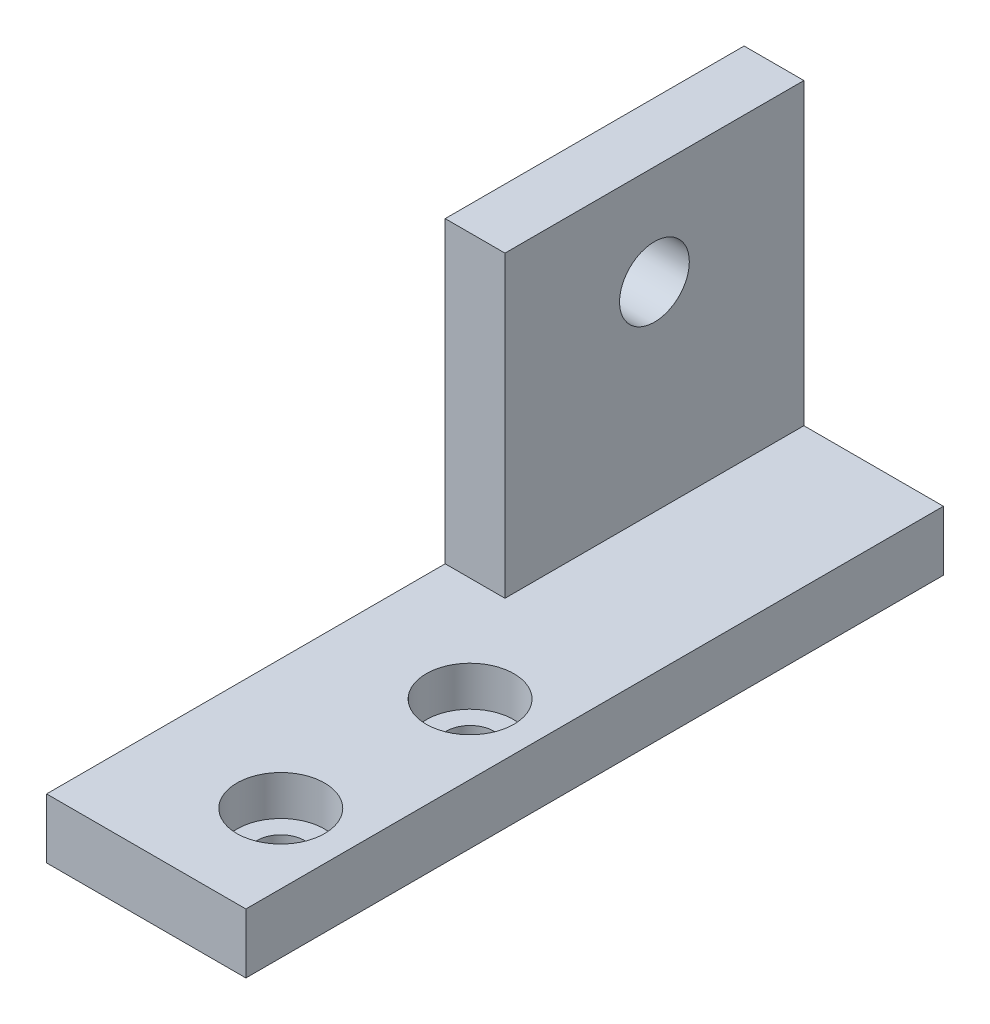
SolidWorks part; units mm, degrees
ref_plane "Front Plane" through (0, 0, 0) normal (0, 0, 1) x (1, 0, 0)
ref_plane "Top Plane" through (0, 0, 0) normal (0, 1, 0) x (1, 0, 0)
ref_plane "Right Plane" through (0, 0, 0) normal (1, 0, 0) x (0, 0, -1)
sketch "Sketch1" plane through (0, 0, 0) normal (0, 1, 0) x (1, 0, 0)
  line L0 (6.5, 5.25) -> (6.5, 14.75) construction
  line L1 (0, 0) -> (10, 0)
  line L2 (0, 0) -> (0, 20)
  line L3 (0, 20) -> (10, 20)
  line L4 (10, 0) -> (10, 20)
  circle A0 centre (6.5, 5.25) radius 1.175
  circle A1 centre (6.5, 14.75) radius 1.175
  point P9 (6.5, 10)
  point P10 (10, 10)
  dimension "D3" = 9.5
  dimension "D4" = 2.35
  dimension "D5" = 2.35
  dimension "D6" = 6.5
  dimension "D1" = 20
  dimension "D2" = 10
extrude "Boss-Extrude1" add sketch "Sketch1" along normal blind 3
sketch "Sketch2" plane through (0, 3, 0) normal (0, 1, 0) x (1, 0, 0)
  point P0 (6.5, 14.75)
  point P1 (6.5, 5.25)
hole_wizard "CBORE for M2 SHCS1" positions "Sketch2" profile "Sketch3" counterbore size "M2" standard "ANSI Metric" end condition through all
sketch "Sketch3" plane through (6.5, 3, -14.75) normal (1, 0, 0) x (0, 0, 1)
  line L0 (0, 0) -> (0, 3)
  line L1 (0, 3) -> (1.2, 3)
  line L3 (1.2, 3) -> (1.2, 2)
  line L4 (1.2, 2) -> (2.2, 2)
  line L5 (2.2, 2) -> (2.2, 0)
  line L7 (2.2, 0) -> (0, 0)
  line L11 (0, -6.35) -> (0, 107.95) construction
  dimension "Thru Hole Dia." = 2.4
  dimension "Thru Hole Depth" = 3
  dimension "C'Bore Dia." = 4.4
  dimension "C'Bore Depth" = 2
sketch "Sketch6" plane through (0, 0, -20) normal (0, 0, -1) x (-1, 0, 0)
  line L1 (0, 0) -> (-10, 0)
  line L2 (0, 0) -> (0, 3)
  line L3 (0, 3) -> (-10, 3)
  line L4 (-10, 0) -> (-10, 3)
  line L5 (-10, 3) -> (0, 3) construction
  line L6 (-10, 3) -> (-10, 0) construction
  point P5 (-10.0485, 3.0247)
  point P6 (-9.5691, 3)
  dimension "D1" = 0
extrude "Boss-Extrude2" add sketch "Sketch6" along normal blind 15
sketch "Sketch8" plane through (0, 3, 0) normal (0, 1, 0) x (1, 0, 0)
  line L2 (0, 35) -> (3, 35)
  line L3 (0, 35) -> (0, 20)
  line L4 (0, 20) -> (3, 20)
  line L5 (3, 35) -> (3, 20)
  dimension "D1" = 3
extrude "Boss-Extrude3" add sketch "Sketch8" along normal blind 15
sketch "Sketch9" plane through (3, 0, 0) normal (1, 0, 0) x (0, 0, -1)
  line L0 (20, 18) -> (35, 18) construction
  line L1 (0, 3) -> (35, 3) construction
  circle A0 centre (27.5, 13) radius 1.75
  point P2 (0, 0)
  point P5 (27.5, 18)
  dimension "D1" = 10
extrude "Cut-Extrude1" cut sketch "Sketch9" against normal through all
